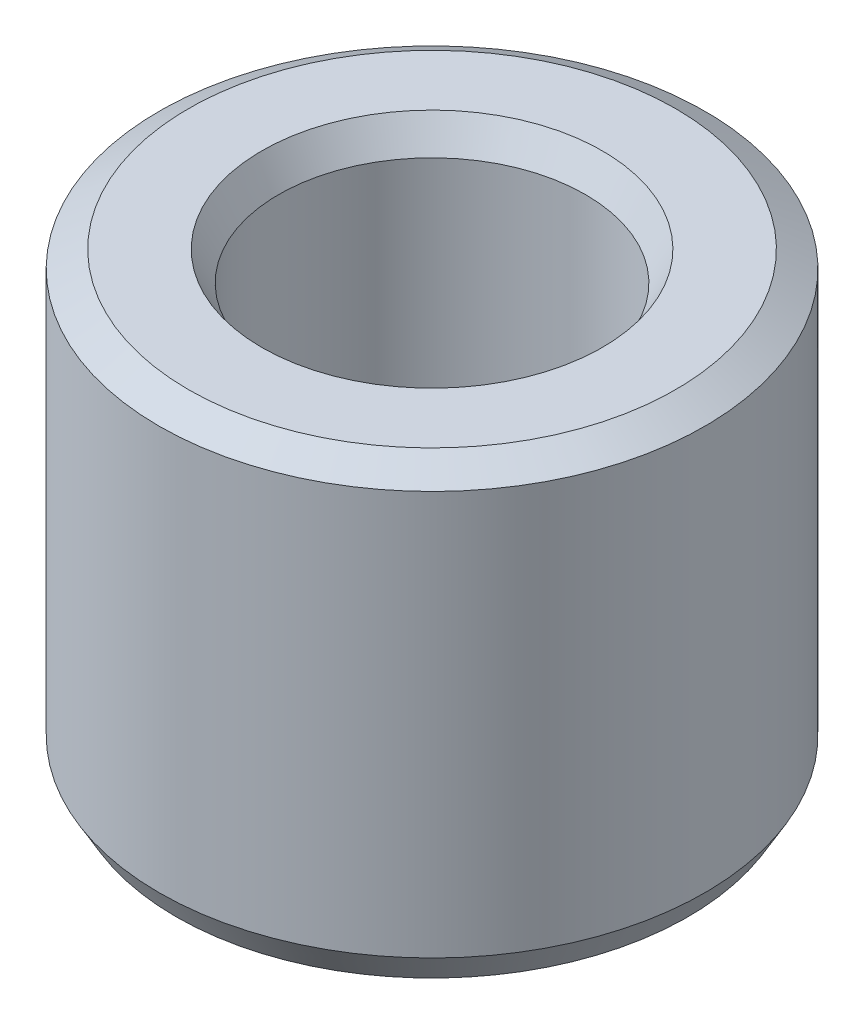
SolidWorks part; units mm, degrees
ref_plane "Front Plane" through (0, 0, 0) normal (0, 0, 1) x (1, 0, 0)
ref_plane "Top Plane" through (0, 0, 0) normal (0, 1, 0) x (1, 0, 0)
ref_plane "Right Plane" through (0, 0, 0) normal (1, 0, 0) x (0, 0, -1)
sketch "Sketch1" plane through (0, 0, 0) normal (0, 1, 0) x (1, 0, 0)
  circle A0 centre (0, 0) radius 47.5
  dimension "SLEEVE_OD" = 95
extrude "Boss-Extrude1" add sketch "Sketch1" along normal blind 78.3974
sketch "Sketch2" plane through (0, 0, 0) normal (0, 1, 0) x (1, 0, 0)
  circle A0 centre (0, 0) radius 26.6996
  dimension "BORE_D" = 53.3991
extrude "Cut-Extrude1" cut sketch "Sketch2" along normal through all
chamfer "Chamfer1" distance 2.9506 angle 60 4 edges at (0, 78.3974, 26.6996) (0, 0, 26.6996) (0, 0, 47.5) (0, 78.3974, 47.5) first distance on face at (0, 78.3974, 26.6996) first distance on face at (0, 0, 26.6996) first distance on face at (0, 78.3974, 47.5)
